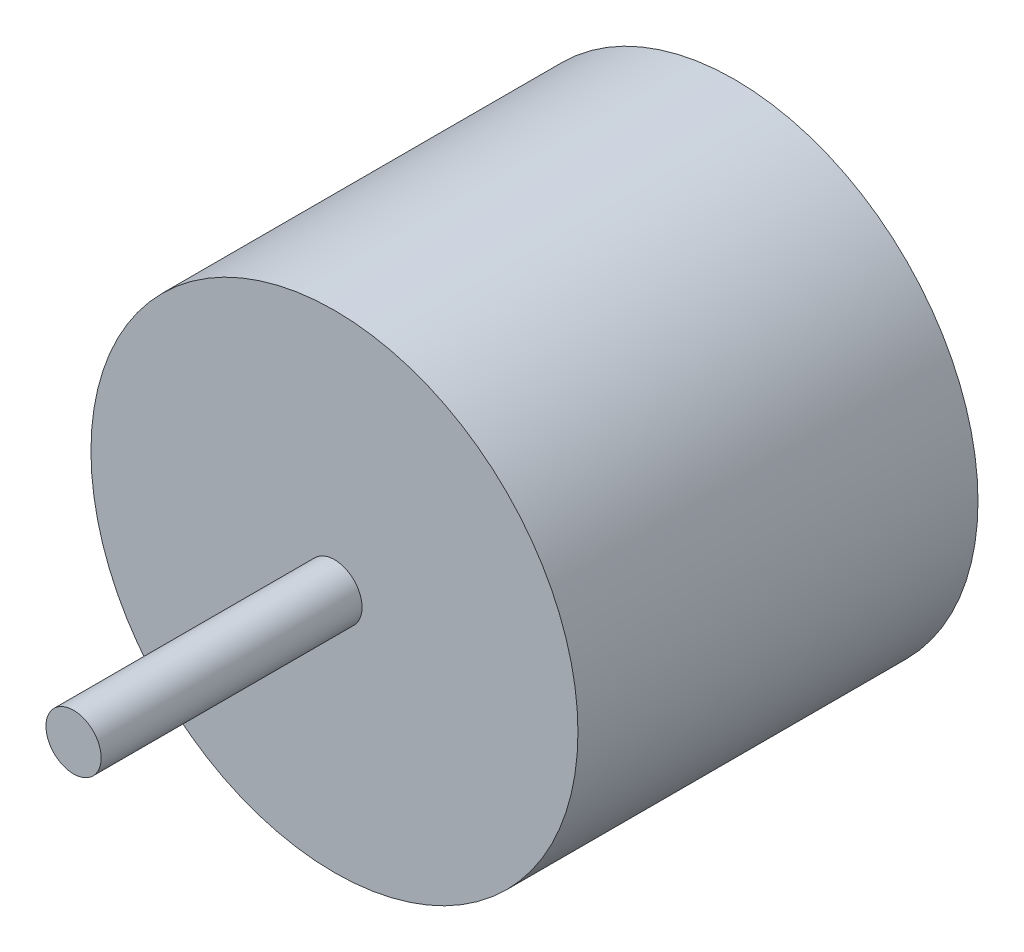
SolidWorks part; units mm, degrees
material "6061 Alloy"
ref_plane "Front Plane" through (0, 0, 0) normal (0, 0, 1) x (1, 0, 0)
ref_plane "Top Plane" through (0, 0, 0) normal (0, 1, 0) x (1, 0, 0)
ref_plane "Right Plane" through (0, 0, 0) normal (1, 0, 0) x (0, 0, -1)
sketch "Sketch1" plane through (0, 0, 0) normal (0, 0, 1) x (1, 0, 0)
  circle A0 centre (0, 0) radius 14
  circle A1 centre (0, 0) radius 1.5875
  dimension "D1" = 3.175
  dimension "D2" = 28
extrude "Boss-Extrude1" add sketch "Sketch1" against normal blind 23 contours A1 | A0 A1 region at (-13.604, 0, 0) region at (0, 0, 0)
extrude "Boss-Extrude2" add sketch "Sketch1<3>" along normal blind 15 contours A1 region at (0, 0, 0)
sketch "Sketch1<3>" plane through (0, 0, 0) normal (0, 0, 1) x (1, 0, 0) same geometry as "Sketch1"
ref_axis "Axis1" through (0, 0, -23) along (0, 0, 1)
